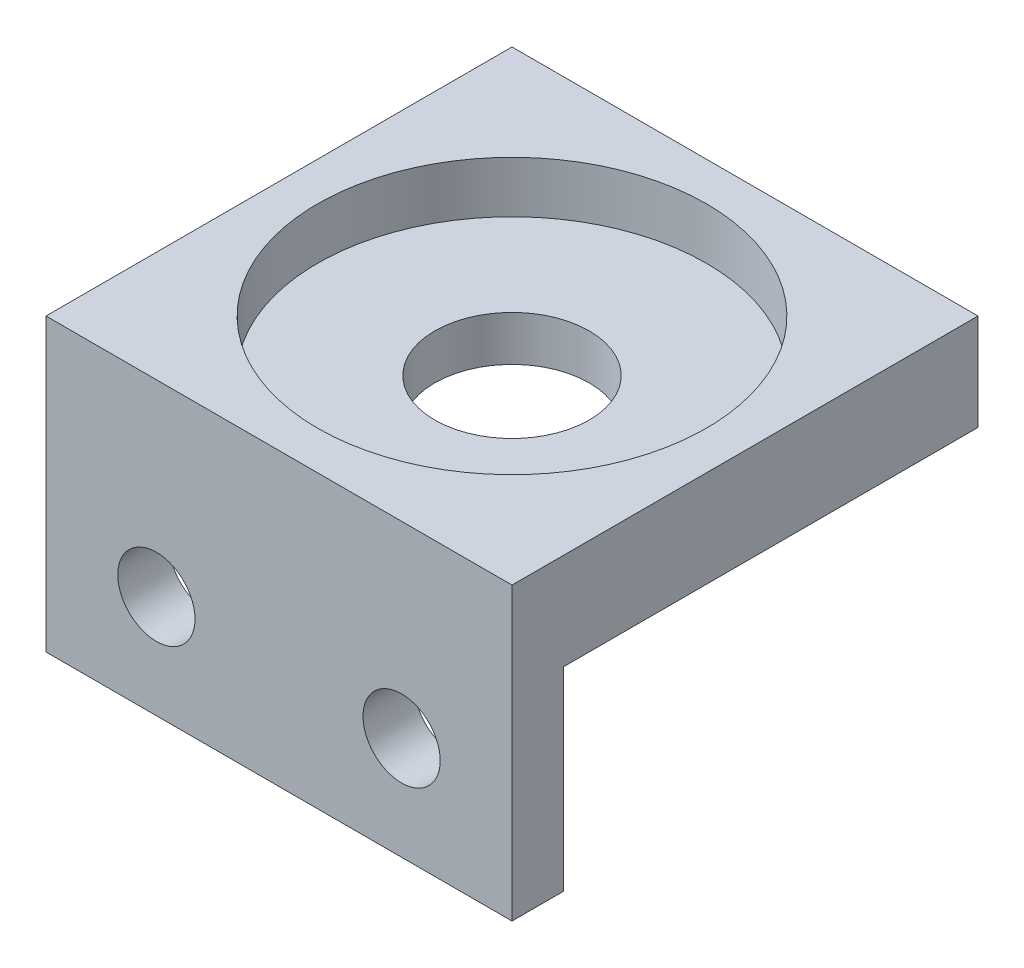
SolidWorks part; units mm, degrees
ref_plane "Front Plane" through (0, 0, 0) normal (0, 0, 1) x (1, 0, 0)
ref_plane "Top Plane" through (0, 0, 0) normal (0, 1, 0) x (1, 0, 0)
ref_plane "Right Plane" through (0, 0, 0) normal (1, 0, 0) x (0, 0, -1)
sketch "Sketch2" plane through (0, 0, 0) normal (0, 1, 0) x (1, 0, 0)
  line L0 (-9.05, 9.05) -> (9.05, 9.05) construction
  line L1 (-9.05, 0) -> (9.05, 0)
  line L2 (-9.05, 0) -> (-9.05, 18.1)
  line L3 (-9.05, 18.1) -> (9.05, 18.1)
  line L4 (9.05, 0) -> (9.05, 18.1)
  circle A0 centre (0, 9.05) radius 7.55
  circle A2 centre (0, 9.05) radius 3
  point P4 (0, 0)
  point P11 (0, 9.05)
  dimension "D1" = 15.1
  dimension "D2" = 1.5
  dimension "D3" = 1.5
  dimension "D4" = 6
extrude "Boss-Extrude1" add sketch "Sketch2" along normal blind 3.75 contours A0 L0 | L0 A0 | L0 L2 L1 L4 A0 | L2 L0 A0 L4 L3 region at (0, 0, -12.6164) region at (0, 0, -5.4836) region at (0, 0, -16.8024) region at (8.3, 0, -8.8476)
extrude "Cut-Extrude1" cut sketch "Sketch2<3>" against normal blind 2 from surface contours L0 A0 | A0 L0 region at (0, 0, -12.6164) region at (0, 0, -5.4836) starting at face at (0, 3.75, -9.05)
sketch "Sketch2<3>" plane through (0, 0, 0) normal (0, 1, 0) x (1, 0, 0) same geometry as "Sketch2"
sketch "Sketch3" plane through (0, 0, 0) normal (0, 0, 1) x (1, 0, 0)
  line L0 (-9.05, 0) -> (-9.05, -7.5525)
  line L1 (-9.05, -7.5525) -> (9.05, -7.5525)
  line L2 (9.05, -7.5525) -> (9.05, 0)
  line L3 (-4.7625, -3.5525) -> (4.7625, -3.5525) construction
  line L4 (0, -3.5525) -> (0, 0) construction
  line L5 (-9.05, 3.75) -> (9.05, 3.75) construction
  line L6 (0, -7.5525) -> (0, -3.5525) construction
  circle A0 centre (-4.7625, -3.5525) radius 1.5
  circle A1 centre (4.7625, -3.5525) radius 1.5
  line M3 (-9.05, 0) -> (9.05, 0)
  dimension "D3" = 2.5
  dimension "D4" = 3
  dimension "D1" = 9.525
  dimension "D2" = 7.3025
extrude "Boss-Extrude2" add sketch "Sketch3" against normal blind 2 contours L1 L2 L0 A1 A0 M3 region at (0, -3.8021, 0)
sketch "Sketch5" plane through (0, 0, 0) normal (1, 0, 0) x (0, 0, -1)
  line L0 (2, 0) -> (2, -7.5525)
  line L1 (6.05, 0) -> (2, 0)
  line L2 (6.05, 0) -> (12.05, 0) construction
  arc A0 (2, -7.5525) -> (6.05, 0) centre (11.067, -7.5525) cw
extrude "Boss-Extrude3" add sketch "Sketch5" along normal mid plane 2
equation "\"D1@Boss-Extrude1\"=1.5mm+2mm+.25mm"
